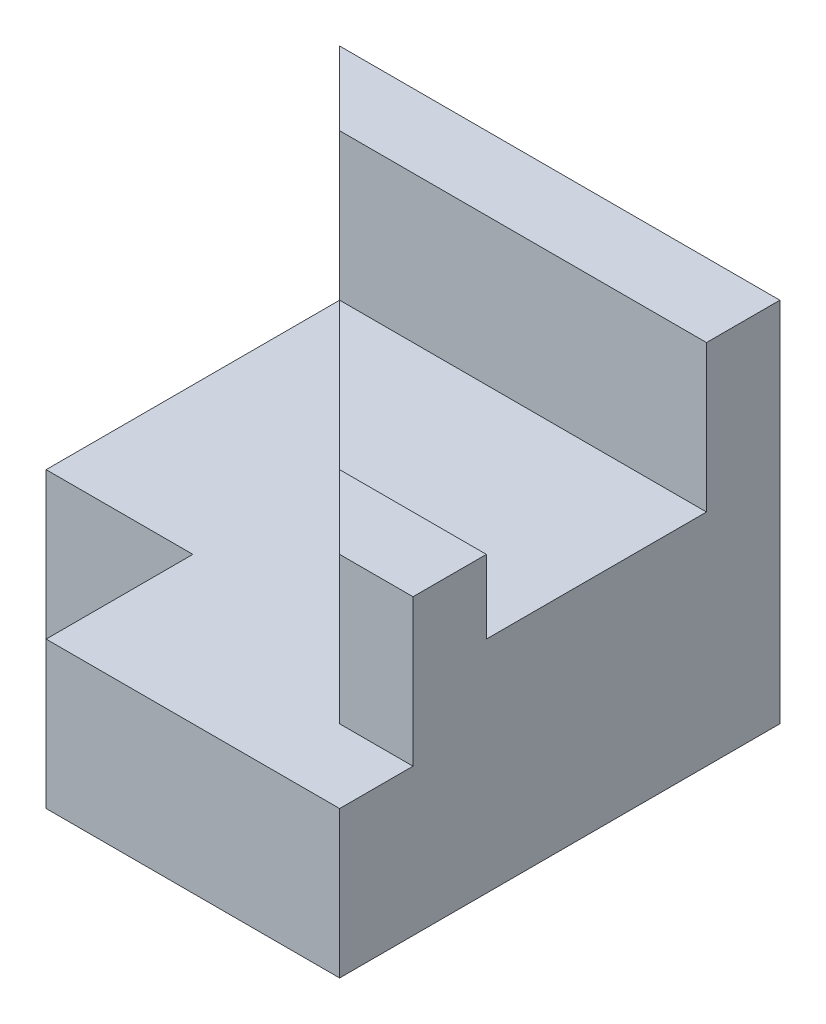
SolidWorks part; units mm, degrees
ref_plane "Front Plane" through (0, 0, 0) normal (0, 0, 1) x (1, 0, 0)
ref_plane "Top Plane" through (0, 0, 0) normal (0, 1, 0) x (1, 0, 0)
ref_plane "Right Plane" through (0, 0, 0) normal (1, 0, 0) x (0, 0, -1)
sketch "Sketch1" plane through (0, 0, 0) normal (0, 0, 1) x (1, 0, 0)
  line L0 (120, -20) -> (-40, -20)
  line L1 (120, 100) -> (-120, 100)
  line L2 (120, 100) -> (120, -100)
  line L3 (120, -100) -> (-120, -100)
  line L4 (-120, 100) -> (-120, -100)
  line L5 (120, 100) -> (-120, -100) construction
  line L6 (120, -100) -> (-120, 100) construction
  line L7 (-40, -20) -> (-40, -100)
  line L8 (-40, -20) -> (-120, -20)
  line L9 (80, -20) -> (80, 60)
  line L10 (80, 60) -> (120, 60)
  point P0 (0, 0)
  dimension "D1" = 200
  dimension "D2" = 240
extrude "Boss-Extrude1" add sketch "Sketch1" along normal blind 120 contours L0 L7 L3 L2 region at (40, -60, 0)
extrude "Boss-Extrude2" add sketch "Sketch1<3>" along normal blind 40 contours L7 L8 L4 L3 region at (-80, -60, 0)
sketch "Sketch1<3>" plane through (0, 0, 0) normal (0, 0, 1) x (1, 0, 0) same geometry as "Sketch1"
extrude "Boss-Extrude3" add sketch "Sketch1<4>" against normal blind 120 contours L0 L7 L3 L2 region at (40, -60, 0)
sketch "Sketch1<4>" plane through (0, 0, 0) normal (0, 0, 1) x (1, 0, 0) same geometry as "Sketch1"
extrude "Boss-Extrude4" add sketch "Sketch1<5>" against normal blind 120 contours L7 L8 L4 L3 region at (-80, -60, 0)
sketch "Sketch1<5>" plane through (0, 0, 0) normal (0, 0, 1) x (1, 0, 0) same geometry as "Sketch1"
sketch "Sketch4" plane through (0, -20, 0) normal (0, 1, 0) x (1, 0, 0)
  line L0 (120, -80) -> (80, -80)
  line L1 (120, -120) -> (120, 120) construction
  line L2 (-120, 120) -> (80, -80)
  line L3 (120, -40) -> (40, -40)
  line L5 (120, 80) -> (-80, 80)
  line M2 (120, 120) -> (-120, 120)
  line M7 (120, -120) -> (120, 120)
extrude "Boss-Extrude7" add sketch "Sketch4" along normal blind 80 contours L3 L2 L0 M7 region at (88.8889, -20, 57.7778)
extrude "Boss-Extrude8" add sketch "Sketch4<3>" along normal blind 120 contours L5 L2 M7 M2 region at (9.697, -20, -100.6061)
sketch "Sketch4<3>" plane through (0, -20, 0) normal (0, 1, 0) x (1, 0, 0) same geometry as "Sketch4"
extrude "Boss-Extrude9" add sketch "Sketch4<4>" along normal blind 40 contours L5 L2 L3 M7 region at (45.7143, -20, -28.5714)
sketch "Sketch4<4>" plane through (0, -20, 0) normal (0, 1, 0) x (1, 0, 0) same geometry as "Sketch4"
